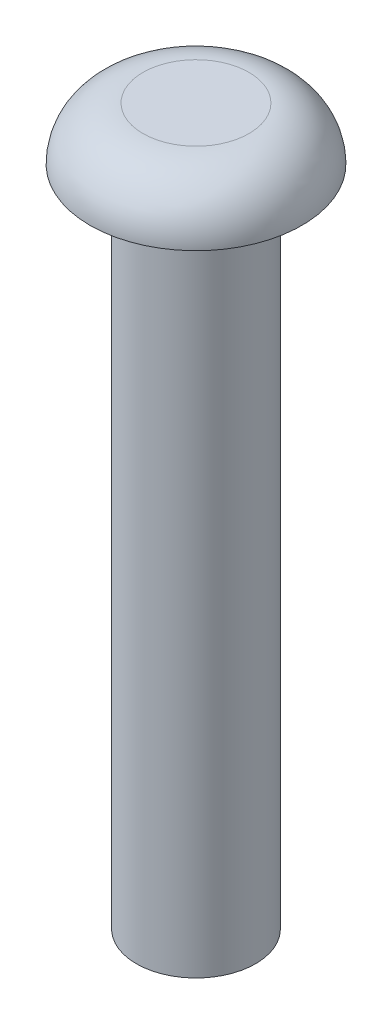
SolidWorks part; units mm, degrees
ref_plane "Front Plane" through (0, 0, 0) normal (0, 0, 1) x (1, 0, 0)
ref_plane "Top Plane" through (0, 0, 0) normal (0, 1, 0) x (1, 0, 0)
ref_plane "Right Plane" through (0, 0, 0) normal (1, 0, 0) x (0, 0, -1)
sketch "Sketch1" plane through (0, 0, 0) normal (0, 1, 0) x (1, 0, 0)
  circle A0 centre (0, 0) radius 2.25
  dimension "D1" = 4.5
extrude "Boss-Extrude1" add sketch "Sketch1" along normal blind 25
sketch "Sketch2" plane through (0, 25, 0) normal (0, 1, 0) x (1, 0, 0)
  circle A0 centre (0, 0) radius 4
  dimension "D1" = 8
extrude "Boss-Extrude2" add sketch "Sketch2" along normal blind 2
fillet "Fillet1" radius 2 1 edges at (0, 27, 4)
